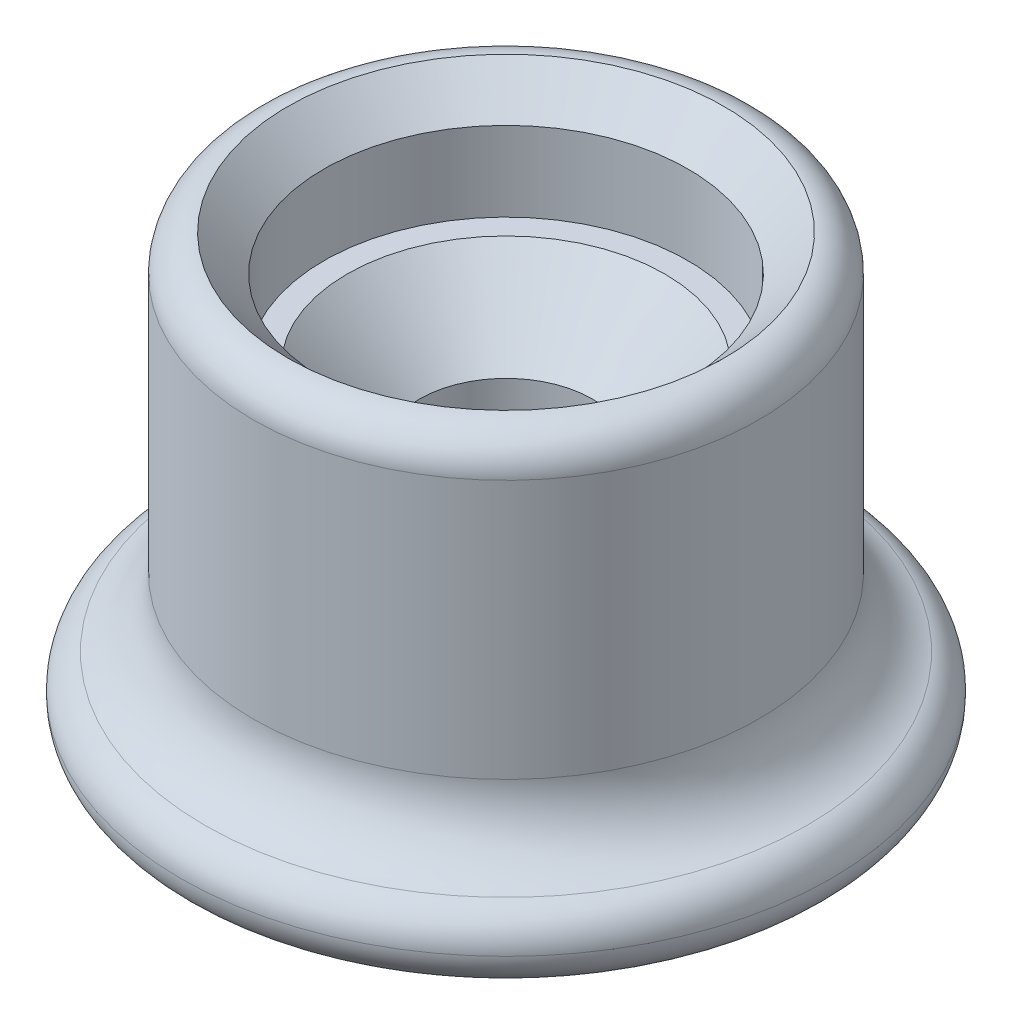
SolidWorks part; units mm, degrees
other "Markup1"
sketch "Sketch7" plane through (7.1437, 9.5244, 7.1437) normal (0.2948, 0.5406, 0.7879) x (0.2266, -0.8406, 0.492)
ref_plane "Front Plane" through (0, 0, 0) normal (0, 0, 1) x (1, 0, 0)
ref_plane "Top Plane" through (0, 0, 0) normal (0, 1, 0) x (1, 0, 0)
ref_plane "Right Plane" through (0, 0, 0) normal (1, 0, 0) x (0, 0, -1)
sketch "Sketch4" plane through (0, 0, 0) normal (0, 1, 0) x (1, 0, 0)
  circle A0 centre (0, 0) radius 5.5562
  circle A1 centre (0, 0) radius 1.905
  dimension "D1" = 11.1125
  dimension "D2" = 3.81
extrude "Boss-Extrude3" add sketch "Sketch4" along normal blind 9.525
sketch "Sketch5" plane through (0, 0, 0) normal (0, -1, 0) x (-1, 0, 0)
  circle A1 centre (0, 0) radius 1.905 construction
  circle A2 centre (0, 0) radius 7.1437
  circle A3 centre (0, 0) radius 7.1437
  circle A4 centre (0, 0) radius 1.905
  dimension "D1" = 1.5875
extrude "Boss-Extrude4" add sketch "Sketch5" against normal blind 1.5875
fillet "Fillet4" radius 0.7937 3 edges at (0, 0, -7.1437) (0, 1.5875, -7.1437) (0, 9.525, 5.5562)
fillet "Fillet5" radius 1.5875 1 edges at (0, 1.5875, -5.5562)
sketch "Sketch6" plane through (0, 9.525, 0) normal (0, 1, 0) x (1, 0, 0)
  circle A0 centre (0, 0) radius 4.0005
  dimension "D1" = 8.001
extrude "Cut-Extrude1" cut sketch "Sketch6" against normal blind 2.54
chamfer "Chamfer1" distance 0.7937 angle 45 1 edges at (0, 9.525, 4.0005)
chamfer "Chamfer2" distance 1.5875 angle 45 1 edges at (0, 6.985, 1.905)
equation "\".0625n\"=0.375"
